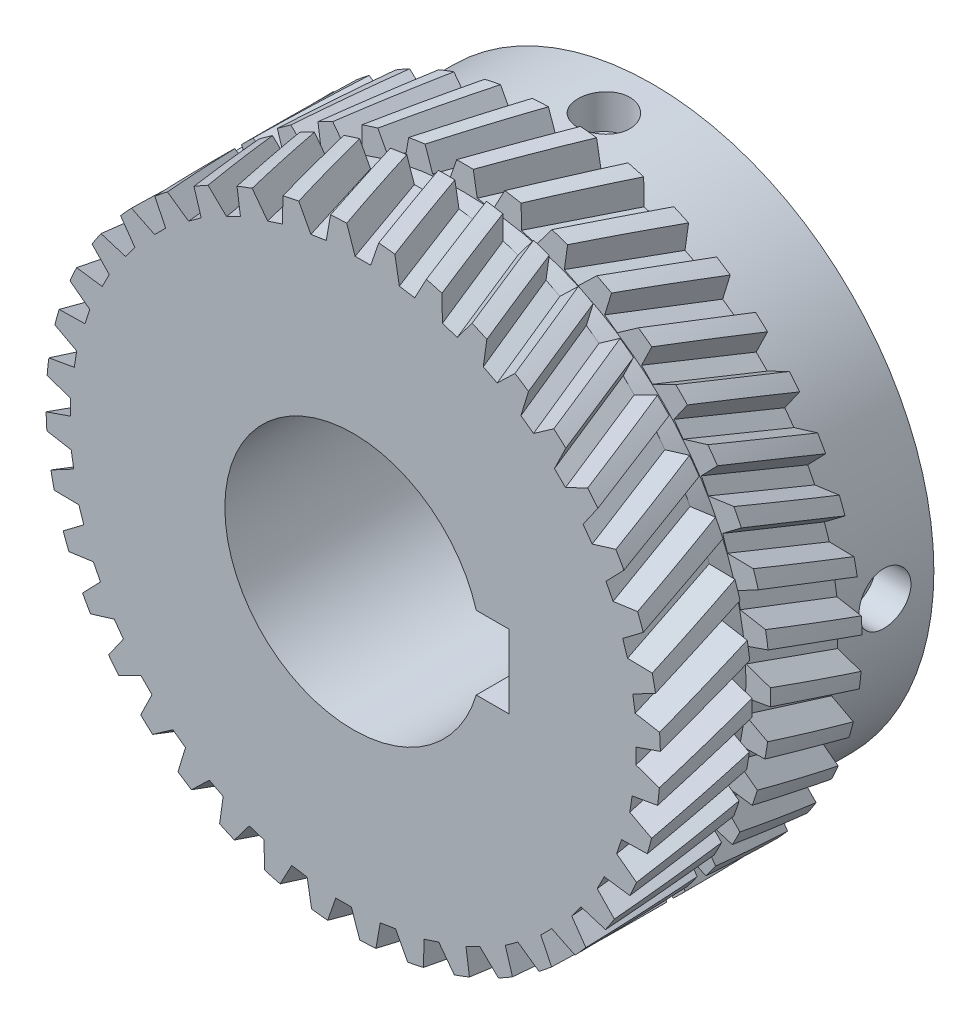
SolidWorks part; units mm, degrees
material "Plain Carbon Steel"
ref_plane "Front Plane" through (0, 0, 0) normal (0, 0, 1) x (1, 0, 0)
ref_plane "Top Plane" through (0, 0, 0) normal (0, 1, 0) x (1, 0, 0)
ref_plane "Right Plane" through (0, 0, 0) normal (1, 0, 0) x (0, 0, -1)
sketch "Sketch1" plane through (0, 0, 0) normal (0, 0, 1) x (1, 0, 0)
  circle A0 centre (0, 0) radius 50.2412
  dimension "D1" = 100.4824
extrude "Boss-Extrude1" add sketch "Sketch1" along normal blind 32.9946
sketch "Sketch2" plane through (0, 0, 0) normal (0, 0, -1) x (-1, 0, 0)
  circle A0 centre (0, 0) radius 45.974
  dimension "D1" = 91.948
extrude "Boss-Extrude2" add sketch "Sketch2" along normal blind 16.002
ref_plane "Plane1" through (50.2412, 0, 0) normal (1, 0, 0) x (0, 0, -1)
sketch "Sketch4" plane through (50.2412, 0, 0) normal (1, 0, 0) x (0, 0, -1)
  line L0 (-16.4946, 6.9104) -> (1.5, 0.5362)
  line L1 (1.5, 0.5362) -> (1.5, -4.7681)
  line L3 (1.5, -4.7681) -> (-16.4946, 1.6061)
  line L4 (-16.4946, 1.6061) -> (-34.4946, -4.7681)
  line L5 (-32.9946, 50.2412) -> (-32.9946, -50.2412) construction
  line L6 (-34.4946, -4.7681) -> (-34.4946, 0.5362)
  line L7 (-34.4946, 0.5362) -> (-16.4946, 6.9104)
  line L8 (0, -50.2412) -> (0, 50.2412) construction
  dimension "D1" = 5
  dimension "D2" = 16.5
  dimension "D3" = 1.5
  dimension "D4" = 1.5
extrude "Cut-Extrude1" cut sketch "Sketch4" against normal blind 4 draft 18
pattern_circular "CirPattern2" count 40 over 360 about axis through (0, 0, 32.9946) along (0, 0, -1) of "Cut-Extrude1"
ref_plane "Plane4" through (0, 0, 16.4973) normal (0, 0, 1) x (1, 0, 0)
sketch "Sketch17" plane through (0, 0, 16.4973) normal (0, 0, 1) x (1, 0, 0)
  circle A0 centre (0, 0) radius 46.2422
  circle A1 centre (0, 0) radius 51.9728
extrude "Cut-Extrude8" cut sketch "Sketch17" against normal blind 1.4986 and the other way blind 1.4986
sketch "Sketch6" plane through (0, 0, -16.002) normal (0, 0, -1) x (-1, 0, 0)
  line L1 (-20.1246, 6) -> (-25.5, 6)
  line L3 (-20.1246, -6) -> (-25.5, -6)
  line L4 (-25.5, 6) -> (-25.5, -6)
  arc A0 (-20.1246, -6) -> (-20.1246, 6) centre (0, 0) ccw
  dimension "D1" = 42
  dimension "D2" = 25.5
  dimension "D3" = 12
extrude "Cut-Extrude3" cut sketch "Sketch6" against normal through all
ref_plane "Plane2" through (0, 20, 0) normal (0, 1, 0) x (1, 0, 0)
sketch "Sketch10" plane through (50.2412, 0, 0) normal (1, 0, 0) x (0, 0, -1)
  line L0 (16.002, -45.974) -> (16.002, 45.974) construction
  circle A0 centre (8.002, 0) radius 4.25
  dimension "D1" = 8.5
  dimension "D2" = 8
extrude "Cut-Extrude6" cut sketch "Sketch10" against normal blind 10
ref_plane "Plane3" through (0, 50.2412, 0) normal (0, 1, 0) x (1, 0, 0)
sketch "Sketch11" plane through (0, 50.2412, 0) normal (0, 1, 0) x (1, 0, 0)
  line L0 (45.974, 16.002) -> (-45.974, 16.002) construction
  circle A0 centre (0, 8.002) radius 4.25
  dimension "D1" = 8.5
  dimension "D2" = 8
extrude "Cut-Extrude7" cut sketch "Sketch11" against normal blind 10
hole_wizard "M8 Tapped Hole1" positions "Sketch13" profile "Sketch12" tap size "M8" standard "Peddi DIN"
sketch "Sketch13" plane through (40.2412, 0, 0) normal (1, 0, 0) x (0, 0, -1)
  circle A0 centre (8.002, 0) radius 4.25 construction
  point P0 (8.002, 0)
sketch "Sketch12" plane through (40.2412, 0, -8.002) normal (0, 1, 0) x (0, 0, -1)
  line L0 (0, 0) -> (0, 35.0379)
  line L1 (0, 35.0379) -> (3.4, 32.995)
  line L2 (3.4, 32.995) -> (3.4, 0)
  line L5 (3.4, 0) -> (0, 0)
  line L10 (0, 35.0379) -> (-3.4, 32.995) construction
  line L11 (0, -6.35) -> (0, 107.95) construction
  dimension "Tap Drill Dia." = 6.8
  dimension "Tap Drill Depth" = 32.995
  dimension "Drill Angle" = 118
cosmetic thread "Hole Thread3" parameters "D1"=15.2412, "D2"=8
hole_wizard "M8 Tapped Hole2" positions "Sketch15" profile "Sketch14" tap size "M8" standard "Peddi DIN"
sketch "Sketch15" plane through (0, 40.2412, 0) normal (0, 1, 0) x (1, 0, 0)
  circle A0 centre (0, 8.002) radius 4.25 construction
  point P0 (0, 8.002)
sketch "Sketch14" plane through (0, 40.2412, -8.002) normal (1, 0, 0) x (0, 0, 1)
  line L0 (0, 0) -> (0, 35.0379)
  line L1 (0, 35.0379) -> (3.4, 32.995)
  line L2 (3.4, 32.995) -> (3.4, 0)
  line L5 (3.4, 0) -> (0, 0)
  line L10 (0, 35.0379) -> (-3.4, 32.995) construction
  line L11 (0, -6.35) -> (0, 107.95) construction
  dimension "Tap Drill Dia." = 6.8
  dimension "Tap Drill Depth" = 32.995
  dimension "Drill Angle" = 118
cosmetic thread "Hole Thread4" parameters "D1"=19.5183, "D2"=8
ref_axis "Axis1" through (0, 0, 32.9946) along (0, 0, -1)
other "Freeze***"
